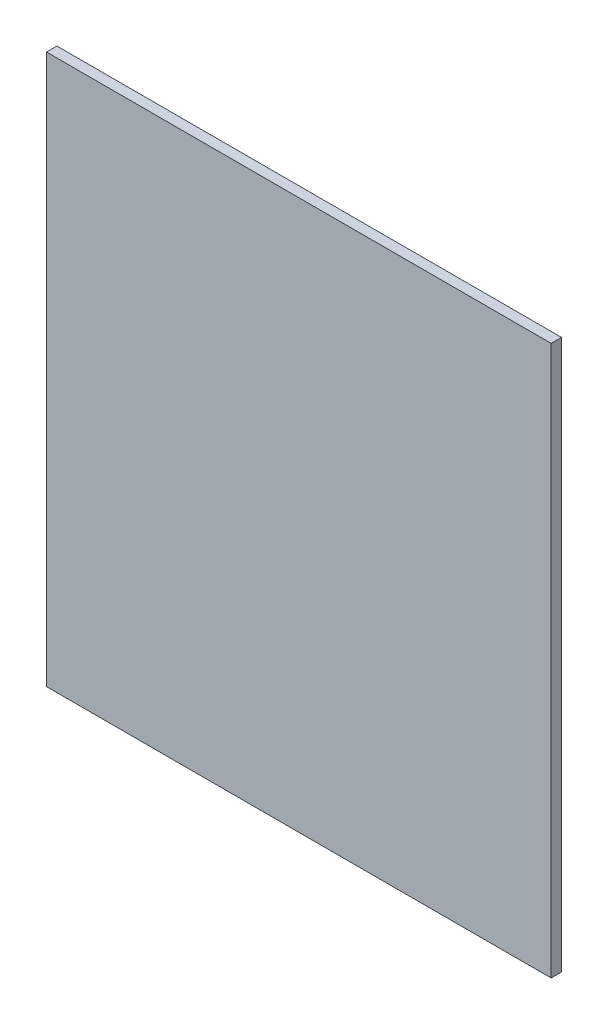
SolidWorks part; units mm, degrees
material "Клен"
ref_plane "Спереди" through (0, 0, 0) normal (0, 0, 1) x (1, 0, 0)
ref_plane "Сверху" through (0, 0, 0) normal (0, 1, 0) x (1, 0, 0)
ref_plane "Справа" through (0, 0, 0) normal (1, 0, 0) x (0, 0, -1)
sketch "Эскиз1" plane through (0, 0, 0) normal (0, 0, 1) x (1, 0, 0)
  line L1 (0, 0) -> (292, 0)
  line L2 (0, 0) -> (0, -318)
  line L3 (0, -318) -> (292, -318)
  line L4 (292, 0) -> (292, -318)
  dimension "D1" = 292
  dimension "D2" = 318
extrude "Бобышка-Вытянуть1" add sketch "Эскиз1" along normal blind 6
